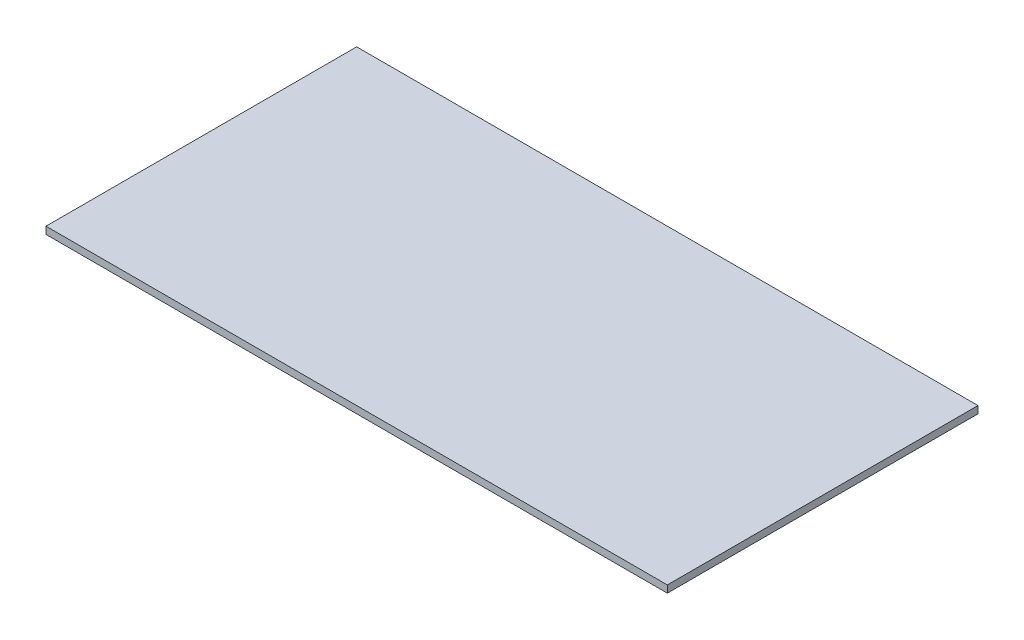
SolidWorks part; units mm, degrees
ref_plane "Front Plane" through (0, 0, 0) normal (0, 0, 1) x (1, 0, 0)
ref_plane "Top Plane" through (0, 0, 0) normal (0, 1, 0) x (1, 0, 0)
ref_plane "Right Plane" through (0, 0, 0) normal (1, 0, 0) x (0, 0, -1)
sketch "Sketch1" plane through (0, 0, 0) normal (0, 1, 0) x (1, 0, 0)
  line L1 (0, 45.589) -> (-260, 45.589)
  line L2 (0, 45.589) -> (0, -84.411)
  line L3 (0, -84.411) -> (-260, -84.411)
  line L4 (-260, 45.589) -> (-260, -84.411)
  dimension "D1" = 260
  dimension "D2" = 130
extrude "Boss-Extrude1" add sketch "Sketch1" along normal blind 3
